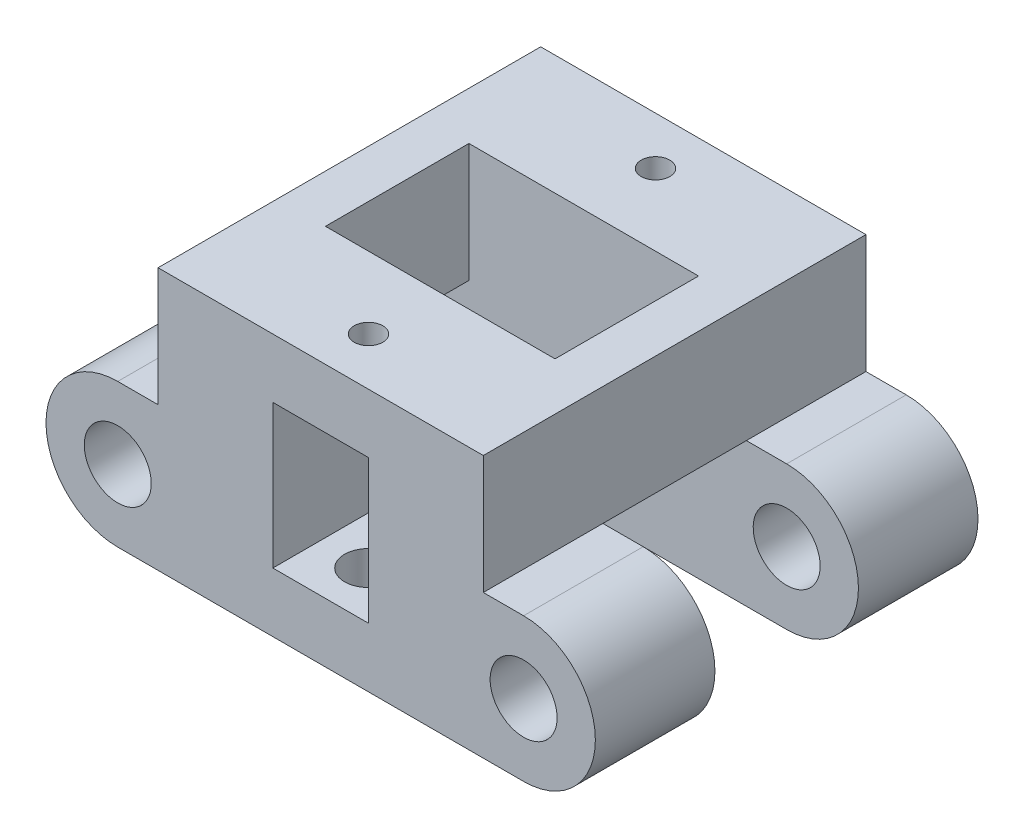
SolidWorks part; units mm, degrees
ref_plane "Front Plane" through (0, 0, 0) normal (0, 0, 1) x (1, 0, 0)
ref_plane "Top Plane" through (0, 0, 0) normal (0, 1, 0) x (1, 0, 0)
ref_plane "Right Plane" through (0, 0, 0) normal (1, 0, 0) x (0, 0, -1)
sketch "Sketch1" plane through (0, 0, 0) normal (0, 0, 1) x (1, 0, 0)
  line L0 (-26.9408, -26.9408) -> (0, 0) construction
  line L1 (0, 0) -> (26.9408, -26.9408) construction
  line L2 (-45.4545, 0) -> (50.5549, 0) construction
  line L7 (-26.9408, -17.4158) -> (-26.9408, 39.7342)
  line L9 (26.9408, 39.7342) -> (26.9408, -17.4158)
  line L11 (15, -48.5349) -> (-15, -48.5349) construction
  line L12 (-26.9408, -36.4658) -> (26.9408, -36.4658)
  line L13 (-26.9408, 39.7342) -> (26.9408, 39.7342)
  circle A0 centre (0, 0) radius 38.1 construction
  circle A1 centre (-26.9408, -26.9408) radius 4.445
  circle A2 centre (26.9408, -26.9408) radius 4.445
  arc A3 (-26.9408, -17.4158) -> (-26.9408, -36.4658) centre (-26.9408, -26.9408) ccw
  arc A4 (26.9408, -36.4658) -> (26.9408, -17.4158) centre (26.9408, -26.9408) ccw
  circle A5 centre (0, 0) radius 50.8 construction
  dimension "D1" = 76.2
  dimension "D4" = 8.89
  dimension "D5" = 8.89
  dimension "D6" = 19.05
  dimension "D7" = 19.05
  dimension "D8" = 57.15
  dimension "D9" = 101.6
  dimension "D2" = 45
  dimension "D3" = 45
  dimension "D10" = 30
extrude "Boss-Extrude1" add sketch "Sketch1" along normal blind 25.4 and the other way blind 25.4
sketch "Sketch9" plane through (0, 0, 25.4) normal (0, 0, 1) x (1, 0, 0)
  line L0 (-26.9408, 39.7342) -> (26.9408, 39.7342) construction
  line L1 (-15.24, 39.7342) -> (15.24, 39.7342)
  line L2 (-15.24, 39.7342) -> (-15.24, 4.6822)
  line L3 (-15.24, 4.6822) -> (15.24, 4.6822)
  line L4 (15.24, 39.7342) -> (15.24, 4.6822)
  line L5 (-15.24, 39.7342) -> (15.24, 4.6822) construction
  line L6 (-15.24, 4.6822) -> (15.24, 39.7342) construction
  point P0 (0, 22.2082)
  dimension "D1" = 30.48
  dimension "D2" = 35.052
extrude "Cut-Extrude6" cut sketch "Sketch9" against normal through all
sketch "Sketch10" plane through (0, 0, 25.4) normal (0, 0, 1) x (1, 0, 0)
  line L0 (-26.9408, 39.7342) -> (-26.9408, -1.6678)
  line L2 (-26.9408, -1.6678) -> (26.9408, -1.6678)
  line L3 (26.9408, 39.7342) -> (26.9408, -17.4158) construction
  line L5 (26.9408, -1.6678) -> (26.9408, 39.7342)
  line L6 (26.9408, 39.7342) -> (15.24, 39.7342)
  line L7 (15.24, 39.7342) -> (15.24, 4.6822)
  line L8 (15.24, 4.6822) -> (-15.24, 4.6822)
  line L9 (-15.24, 4.6822) -> (-15.24, 39.7342)
  line L10 (-15.24, 39.7342) -> (-26.9408, 39.7342)
  dimension "D1" = 6.35
extrude "Boss-Extrude3" add sketch "Sketch10" along normal blind 12.7
mirror "Mirror4" about plane through (0, 0, 0) normal (0, 0, 1) of "Boss-Extrude3"
sketch "Sketch11" plane through (0, 0, 38.1) normal (0, 0, 1) x (1, 0, 0)
  line L1 (-26.9408, 39.7342) -> (-21.59, 39.7342)
  line L2 (-26.9408, 39.7342) -> (-26.9408, -17.4158)
  line L3 (-26.9408, -17.4158) -> (-21.59, -17.4158)
  line L4 (-21.59, 39.7342) -> (-21.59, -17.4158)
  line L5 (-15.24, 4.6822) -> (-15.24, 39.7342) construction
  dimension "D1" = 6.35
extrude "Cut-Extrude7" cut sketch "Sketch11" against normal through all
mirror "Mirror5" about plane through (0, 0, 0) normal (1, 0, 0) of "Cut-Extrude7"
sketch "Sketch12" plane through (0, -36.4658, 0) normal (0, -1, 0) x (1, 0, 0)
  line L0 (15.24, -38.1) -> (15.24, 38.1) construction
  line L1 (-15.24, 9.525) -> (15.24, 9.525)
  line L2 (-15.24, 9.525) -> (-15.24, -9.525)
  line L3 (-15.24, -9.525) -> (15.24, -9.525)
  line L4 (15.24, 9.525) -> (15.24, -9.525)
  line L5 (-15.24, 9.525) -> (15.24, -9.525) construction
  line L6 (-15.24, -9.525) -> (15.24, 9.525) construction
  point P0 (0, 0)
  point P2 (15.24, 9.525)
  dimension "D1" = 19.05
extrude "Cut-Extrude8" cut sketch "Sketch12" against normal through all
sketch "Sketch14" plane through (-21.59, 0, 0) normal (-1, 0, 0) x (0, 0, 1)
  line L0 (-38.1, 4.6822) -> (-9.525, 4.6822) construction
  circle A0 centre (-18.4, 22.4622) radius 1.6
  dimension "D1" = 3.2
  dimension "D2" = 17.78
  dimension "D3" = 18.4
extrude "Cut-Extrude9" cut sketch "Sketch14" against normal through all
mirror "Mirror6" about plane through (0, 0, 0) normal (0, 0, 1) of "Cut-Extrude9"
sketch "Sketch15" plane through (21.59, 0, 0) normal (1, 0, 0) x (0, 0, -1)
  line L0 (0, -17.4158) -> (0, 39.7342) construction
  line L1 (-18.4, 22.4622) -> (18.4, 22.4622) construction
  line L2 (0, 38.1) -> (0, -38.1) construction
  circle A0 centre (0, 22.4622) radius 3.429
  dimension "D1" = 6.858
extrude "Cut-Extrude10" cut sketch "Sketch15" against normal through all
sketch "Sketch18" plane through (0, 4.6822, 0) normal (0, 1, 0) x (1, 0, 0)
  line L0 (-26.9408, 0) -> (26.9408, 0) construction
  line L1 (-15.24, 2.3464) -> (-19.304, 4.6927)
  line L2 (-19.304, 4.6927) -> (-23.368, 2.3464)
  line L3 (-23.368, 2.3464) -> (-23.368, -2.3464)
  line L4 (-23.368, -2.3464) -> (-19.304, -4.6927)
  line L5 (-19.304, -4.6927) -> (-15.24, -2.3464)
  line L6 (-15.24, -2.3464) -> (-15.24, 2.3464)
  line L7 (-15.24, -9.525) -> (-15.24, -38.1) construction
  circle A0 centre (-19.304, 0) radius 4.064 construction
  dimension "D1" = 8.128
extrude "Cut-Extrude11" cut sketch "Sketch18" against normal blind 2.7781
mirror "Mirror7" about plane through (0, 0, 0) normal (1, 0, 0) of "Cut-Extrude11"
hole_wizard "#6 Clearance Hole1" positions "Sketch20" profile "Sketch22" hole size "#6" standard "ANSI Inch" end condition through all
sketch "Sketch20" plane through (0, 1.9041, 0) normal (0, 1, 0) x (1, 0, 0)
  point P0 (0, 19.05)
  dimension "D1" = 19.05
sketch "Sketch22" plane through (0, 1.9041, -19.05) normal (1, 0, 0) x (0, 0, 1)
  line L0 (0, 0) -> (0, 38.3699)
  line L1 (0, 38.3699) -> (1.8986, 38.3699)
  line L2 (1.8986, 38.3699) -> (1.8986, 0)
  line L5 (1.8986, 0) -> (0, 0)
  line L11 (0, -6.35) -> (0, 107.95) construction
  dimension "Thru Hole Dia." = 3.7973
  dimension "Thru Hole Depth" = 38.3699
mirror "Mirror8" about plane through (0, 0, 0) normal (0, 0, 1) of "#6 Clearance Hole1"
sketch "Sketch23" plane through (0, -36.4658, 0) normal (0, -1, 0) x (1, 0, 0)
  circle A0 centre (0, -19.05) radius 3.175
  circle A1 centre (0, 19.05) radius 3.175
  dimension "D1" = 6.35
  dimension "D2" = 6.35
extrude "Cut-Extrude12" cut sketch "Sketch23" against normal blind 22.225
sketch "Sketch24" plane through (0, 0, -38.1) normal (0, 0, -1) x (-1, 0, 0)
  line L1 (-21.59, -1.6678) -> (21.59, -1.6678)
  line L2 (-21.59, -1.6678) -> (-21.59, 39.7342)
  line L3 (-21.59, 39.7342) -> (21.59, 39.7342)
  line L4 (21.59, -1.6678) -> (21.59, 39.7342)
extrude "Cut-Extrude13" cut sketch "Sketch24" against normal through all
sketch "Sketch25" plane through (0, 0, 25.4) normal (0, 0, 1) x (1, 0, 0)
  line L1 (-6.35, -9.525) -> (6.35, -9.525)
  line L2 (-6.35, -9.525) -> (-6.35, -28.575)
  line L3 (-6.35, -28.575) -> (6.35, -28.575)
  line L4 (6.35, -9.525) -> (6.35, -28.575)
  line L5 (-6.35, -9.525) -> (6.35, -28.575) construction
  line L6 (-6.35, -28.575) -> (6.35, -9.525) construction
  point P0 (0, -19.05)
  dimension "D1" = 19.05
  dimension "D2" = 12.7
  dimension "D3" = 19.05
extrude "Cut-Extrude14" cut sketch "Sketch25" against normal up to next
sketch "Sketch26" plane through (21.59, 0, 0) normal (1, 0, 0) x (0, 0, -1)
  line L0 (0, 50.8) -> (0, -50.8) construction
  line L1 (-9.525, -17.4158) -> (9.525, -17.4158)
  line L2 (-9.525, -17.4158) -> (-9.525, -78.4361)
  line L3 (-9.525, -78.4361) -> (9.525, -78.4361)
  line L4 (9.525, -17.4158) -> (9.525, -78.4361)
  line L5 (-9.525, -17.4158) -> (9.525, -78.4361) construction
  line L6 (-9.525, -78.4361) -> (9.525, -17.4158) construction
  line L7 (25.4, -17.4158) -> (-25.4, -17.4158) construction
  point P0 (0, -47.926)
  dimension "D1" = 19.05
extrude "Cut-Extrude15" cut sketch "Sketch26" along normal through all and the other way through all
hole_wizard "#25 (0.1495) Diameter Hole1" positions "Sketch27" profile "Sketch28" hole size "#25" standard "ANSI Inch" end condition up to next
sketch "Sketch27" plane through (0, -36.4658, 0) normal (0, -1, 0) x (-1, 0, 0)
  line L0 (26.9408, -9.525) -> (26.9408, -25.4) construction
  line L1 (26.9408, 25.4) -> (26.9408, 9.525) construction
  line L2 (-26.9408, 25.4) -> (-26.9408, 9.525) construction
  line L3 (-26.9408, -9.525) -> (-26.9408, -25.4) construction
  point P0 (26.9408, -17.4625)
  point P4 (26.9408, 17.4625)
  point P8 (-26.9408, 17.4625)
  point P12 (-26.9408, -17.4625)
sketch "Sketch28" plane through (-26.9408, -36.4658, 17.4625) normal (1, 0, 0) x (0, 0, -1)
  line L0 (0, 0) -> (0, 5.08)
  line L1 (0, 5.08) -> (1.8986, 5.08)
  line L2 (1.8986, 5.08) -> (1.8986, 0)
  line L5 (1.8986, 0) -> (0, 0)
  line L11 (0, -6.35) -> (0, 107.95) construction
  dimension "Thru Hole Dia." = 3.7973
  dimension "Thru Hole Depth" = 5.08
